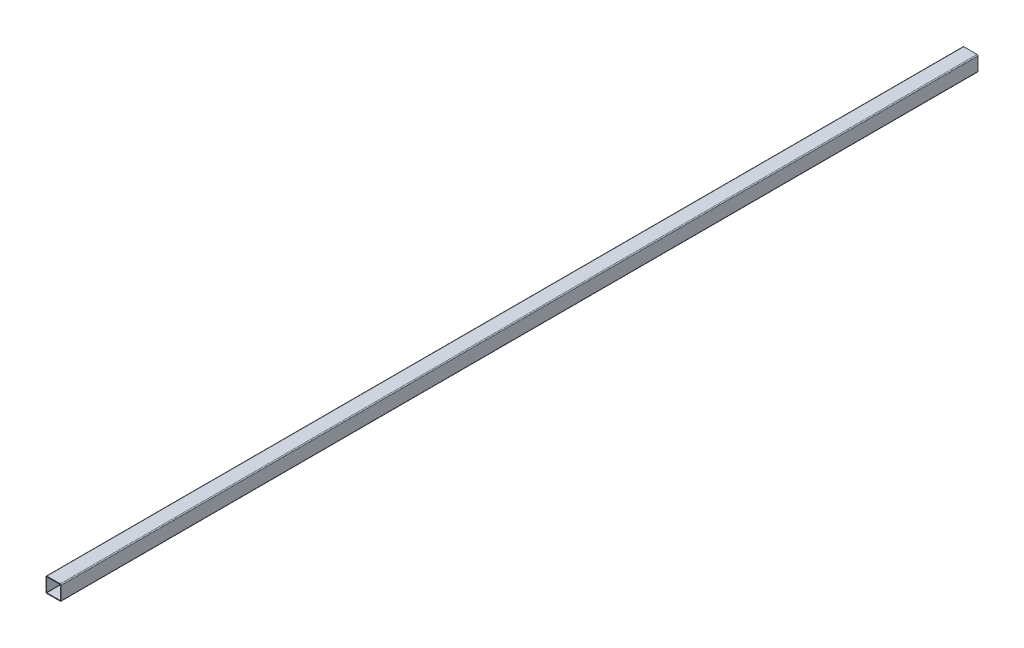
SolidWorks part; units mm, degrees
material "AISI 1010 Steel, hot rolled bar"
ref_plane "Front Plane" through (0, 0, 0) normal (0, 0, 1) x (1, 0, 0)
ref_plane "Top Plane" through (0, 0, 0) normal (0, 1, 0) x (1, 0, 0)
ref_plane "Right Plane" through (0, 0, 0) normal (1, 0, 0) x (0, 0, -1)
sketch "Sketch1" plane through (0, 0, 0) normal (0, 0, 1) x (1, 0, 0)
  line L0 (-14, 14.48) -> (14, 14.48)
  line L1 (-14, -16) -> (14, -16)
  line L2 (-16, -14) -> (-16, 14)
  line L3 (-14, 16) -> (14, 16)
  line L4 (16, -14) -> (16, 14)
  line L5 (-16, -16) -> (16, 16) construction
  line L6 (-16, 16) -> (16, -16) construction
  line L7 (14.48, -14) -> (14.48, 14)
  line L8 (-14, -14.48) -> (14, -14.48)
  line L9 (-14.48, -14) -> (-14.48, 14)
  arc A0 (14, -16) -> (16, -14) centre (14, -14) ccw
  arc A1 (-16, 14) -> (-14, 16) centre (-14, 14) cw
  arc A2 (-16, -14) -> (-14, -16) centre (-14, -14) ccw
  arc A3 (16, 14) -> (14, 16) centre (14, 14) ccw
  arc A4 (14.48, 14) -> (14, 14.48) centre (14, 14) ccw
  arc A5 (14, -14.48) -> (14.48, -14) centre (14, -14) ccw
  arc A6 (-14.48, -14) -> (-14, -14.48) centre (-14, -14) ccw
  arc A7 (-14.48, 14) -> (-14, 14.48) centre (-14, 14) cw
  point P0 (0, 0)
  dimension "D3" = 2
  dimension "D1" = 32
  dimension "D2" = 32
  dimension "D4" = 1.52
extrude "Boss-Extrude1" add sketch "Sketch1" along normal blind 968 and the other way blind 968
